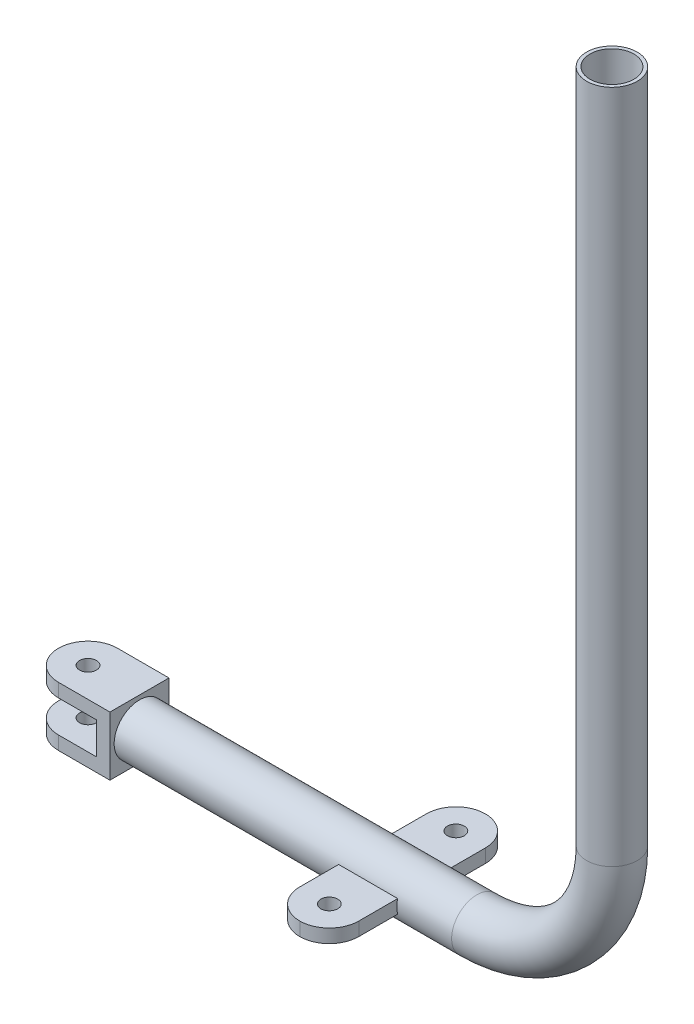
SolidWorks part; units mm, degrees
ref_plane "Front Plane" through (0, 0, 0) normal (0, 0, 1) x (1, 0, 0)
ref_plane "Top Plane" through (0, 0, 0) normal (0, 1, 0) x (1, 0, 0)
ref_plane "Right Plane" through (0, 0, 0) normal (1, 0, 0) x (0, 0, -1)
sketch "Sketch44" plane through (0, 0, 0) normal (0, 0, 1) x (1, 0, 0)
  line L0 (0, 0) -> (200, 0)
  line L1 (280, 80) -> (280, 480)
  arc A0 (200, 0) -> (280, 80) centre (200, 80) ccw
  dimension "D2" = 80
  dimension "D1" = 200
  dimension "D3" = 400
sweep "Sweep-Thin3" add path "Sketch44" circular profile diameter 30 parameters "D1"=2, "D3"=30
sketch "Sketch57" plane through (0, 0, 0) normal (-1, 0, 0) x (0, 0, 1)
  line L1 (-17.5, -17.5) -> (17.5, -17.5)
  line L2 (-17.5, -17.5) -> (-17.5, 17.5)
  line L3 (-17.5, 17.5) -> (17.5, 17.5)
  line L4 (17.5, -17.5) -> (17.5, 17.5)
  line L5 (-17.5, -17.5) -> (17.5, 17.5) construction
  line L6 (-17.5, 17.5) -> (17.5, -17.5) construction
  point P0 (0, 0)
  dimension "D1" = 35
  dimension "D2" = 35
extrude "Boss-Extrude1" add sketch "Sketch57" along normal blind 8
sketch "Sketch58" plane through (-8, 0, 0) normal (-1, 0, 0) x (0, 0, 1)
  line L0 (-17.5, 17.5) -> (-17.5, -17.5) construction
  line L1 (17.5, 17.5) -> (-17.5, 17.5)
  line L2 (17.5, 17.5) -> (17.5, 9.5)
  line L3 (17.5, 9.5) -> (-17.5, 9.5)
  line L4 (-17.5, 17.5) -> (-17.5, 9.5)
  line L5 (39.875, 0) -> (-39.875, 0) construction
  line L6 (17.5, -9.5) -> (-17.5, -9.5)
  line L7 (-17.5, -17.5) -> (-17.5, -9.5)
  line L8 (17.5, -17.5) -> (-17.5, -17.5)
  line L9 (17.5, -17.5) -> (17.5, -9.5)
  dimension "D1" = 8
extrude "Boss-Extrude2" add sketch "Sketch58" along normal blind 40
fillet "Fillet1" radius 17.5 4 edges at (-48, -13.5, 17.5) (-48, -13.5, -17.5) (-48, 13.5, 17.5) (-48, 13.5, -17.5)
sketch "Sketch59" plane through (0, 17.5, 0) normal (0, 1, 0) x (1, 0, 0)
  circle A0 centre (-30.5, 0) radius 5
  arc A1 (-30.5, 17.5) -> (-48, 0) centre (-30.5, 0) ccw construction
  dimension "D1" = 10
extrude "Cut-Extrude1" cut sketch "Sketch59" against normal through all
sketch "Sketch60" plane through (0, 0, 0) normal (0, 0, 1) x (1, 0, 0)
  line L0 (0, -15) -> (0, 15) construction
  line L1 (132.5, -4) -> (167.5, -4)
  line L2 (132.5, -4) -> (132.5, 4)
  line L3 (132.5, 4) -> (167.5, 4)
  line L4 (167.5, -4) -> (167.5, 4)
  line L5 (132.5, -4) -> (167.5, 4) construction
  line L6 (132.5, 4) -> (167.5, -4) construction
  point P0 (150, 0)
  point P5 (0, 0)
  point P6 (0, 0)
  dimension "D1" = 8
  dimension "D2" = 35
  dimension "D3" = 150
extrude "Boss-Extrude3" add sketch "Sketch60" along normal blind 55
fillet "Fillet2" radius 17.5 2 edges at (132.5, 0, 55) (167.5, 0, 55)
sketch "Sketch61" plane through (0, 4, 0) normal (0, 1, 0) x (1, 0, 0)
  circle A0 centre (150, -37.5) radius 5
  arc A1 (150, -55) -> (167.5, -37.5) centre (150, -37.5) ccw construction
  dimension "D1" = 10
extrude "Cut-Extrude2" cut sketch "Sketch61" against normal blind 55
mirror "Mirror1" about plane through (0, 0, 0) normal (0, 0, 1) of "Boss-Extrude3", "Fillet2", "Cut-Extrude2"
